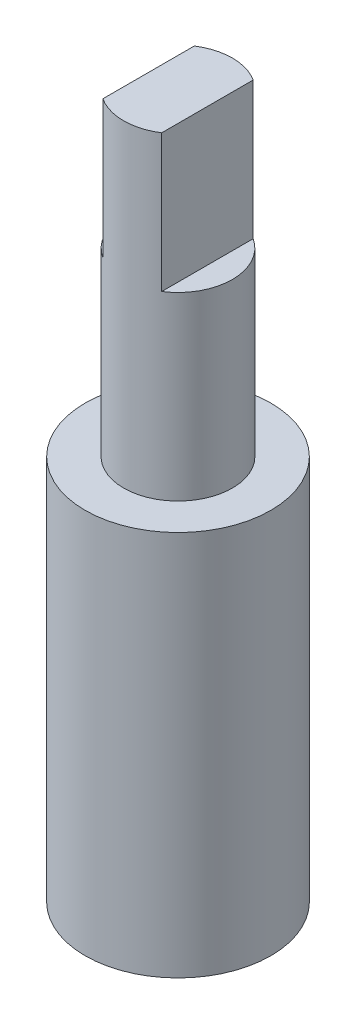
SolidWorks part; units mm, degrees
ref_plane "Front Plane" through (0, 0, 0) normal (0, 0, 1) x (1, 0, 0)
ref_plane "Top Plane" through (0, 0, 0) normal (0, 1, 0) x (1, 0, 0)
ref_plane "Right Plane" through (0, 0, 0) normal (1, 0, 0) x (0, 0, -1)
sketch "Sketch1" plane through (0, 0, 0) normal (0, 1, 0) x (1, 0, 0)
  circle A0 centre (0, 0) radius 3.075
  dimension "D1" = 6.15
extrude "Boss-Extrude1" add sketch "Sketch1" along normal blind 12.77
sketch "Sketch2" plane through (0, 12.77, 0) normal (0, 1, 0) x (1, 0, 0)
  circle A0 centre (0, 0) radius 1.8
  dimension "D1" = 3.6
extrude "Boss-Extrude2" add sketch "Sketch2" along normal blind 5.98
sketch "Sketch3" plane through (0, 18.75, 0) normal (0, 1, 0) x (1, 0, 0)
  line L0 (-0.975, 1.5131) -> (-0.975, -1.5131)
  line L1 (0.975, 1.5131) -> (0.975, -1.5131)
  circle A0 centre (0, 0) radius 1.8 construction
  circle A1 centre (0, 0) radius 1.8 construction
  arc A2 (-0.975, -1.5131) -> (0.975, -1.5131) centre (0, 0) ccw
  arc A3 (0.975, 1.5131) -> (-0.975, 1.5131) centre (0, 0) ccw
  point P4 (-1.8, 0)
  point P5 (1.8, 0)
  dimension "D1" = 1.95
  dimension "D2" = 0.975
extrude "Boss-Extrude3" add sketch "Sketch3" along normal blind 4.55
sketch "Sketch4" plane through (0, 0, 0) normal (0, -1, 0) x (1, 0, 0)
  circle A0 centre (0, 0) radius 2.15
  dimension "D1" = 4.3
extrude "Cut-Extrude1" cut sketch "Sketch4" against normal blind 1.95
